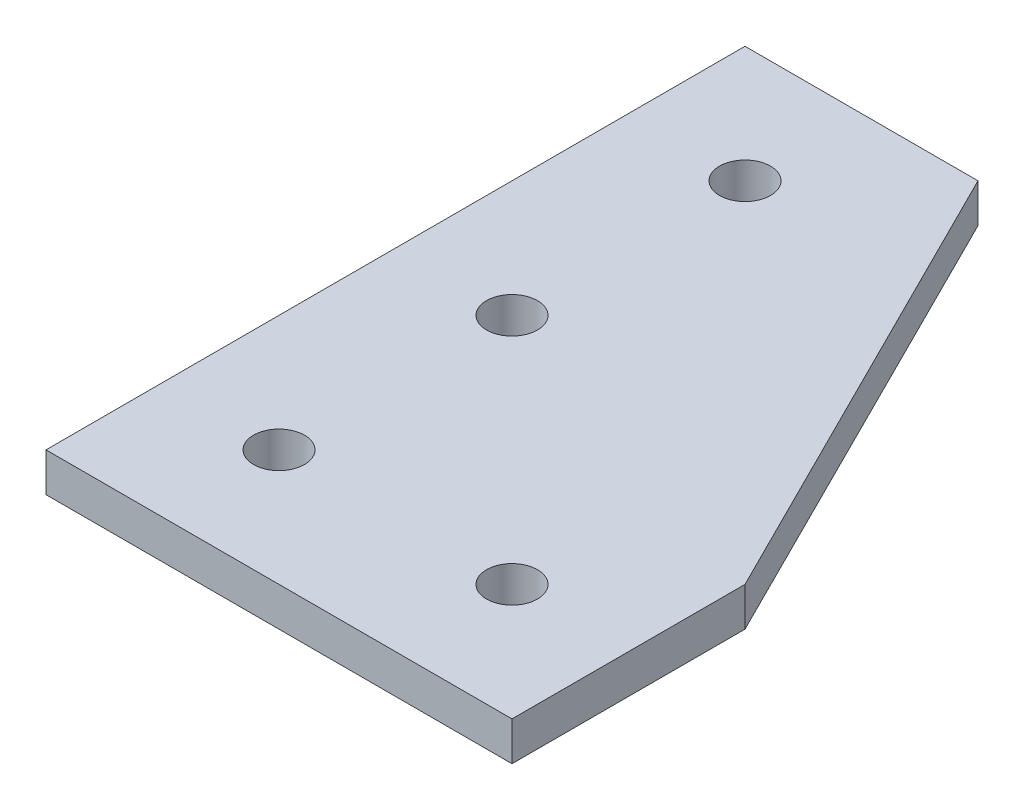
SolidWorks part; units mm, degrees
material "6105-T5 Aluminum"
ref_plane "Front Plane" through (0, 0, 0) normal (0, 0, 1) x (1, 0, 0)
ref_plane "Top Plane" through (0, 0, 0) normal (0, 1, 0) x (1, 0, 0)
ref_plane "Right Plane" through (0, 0, 0) normal (1, 0, 0) x (0, 0, -1)
sketch "Sketch1" plane through (0, 0, 0) normal (0, 0, 1) x (1, 0, 0)
  line L1 (-38.1, -3.175) -> (38.1, -3.175)
  line L2 (-38.1, -3.175) -> (-38.1, 3.175)
  line L3 (-38.1, 3.175) -> (38.1, 3.175)
  line L4 (38.1, -3.175) -> (38.1, 3.175)
  line L5 (-38.1, -3.175) -> (38.1, 3.175) construction
  line L6 (-38.1, 3.175) -> (38.1, -3.175) construction
  point P0 (0, 0)
  dimension "D1" = 76.2
  dimension "D2" = 6.35
extrude "Boss-Extrude1" add sketch "Sketch1" along normal mid plane 114.3
sketch "Sketch8" plane through (0, 3.175, 0) normal (0, 1, 0) x (-1, 0, 0)
  line L0 (0, -57.15) -> (-38.1, 19.05)
  line L1 (-38.1, -57.15) -> (38.1, -57.15) construction
  line L2 (-38.1, 57.15) -> (-38.1, -57.15) construction
  line L3 (-38.1, 19.05) -> (-38.1, -57.15)
  line L4 (-38.1, -57.15) -> (0, -57.15)
  line L5 (-38.1, 57.15) -> (38.1, 57.15) construction
  line L6 (38.1, 57.15) -> (38.1, -57.15) construction
  dimension "D1" = 38.1
  dimension "D2" = 38.1
extrude "Cut-Extrude3" cut sketch "Sketch8" against normal blind 7.62
hole_wizard "21/64 (0.32813) Diameter Hole1" positions "Sketch10" profile "Sketch9" hole size "21/64" standard "Ansi Inch"
sketch "Sketch10" plane through (0, 3.175, 0) normal (0, 1, 0) x (-1, 0, 0)
  point P0 (19.05, 38.1)
  dimension "D1" = 38.1
  dimension "D2" = 19.05
sketch "Sketch9" plane through (-19.05, 3.175, 38.1) normal (1, 0, 0) x (0, 0, 1)
  line L0 (0, 0) -> (0, 8.8539)
  line L1 (0, 8.8539) -> (4.1673, 6.35)
  line L2 (4.1673, 6.35) -> (4.1673, 0)
  line L5 (4.1673, 0) -> (0, 0)
  line L10 (0, 8.8539) -> (-4.1673, 6.35) construction
  line L11 (0, -6.35) -> (0, 1.4053) construction
  dimension "Hole Dia." = 8.3345
  dimension "Hole Depth" = 6.35
  dimension "Drill Angle" = 118
pattern_linear "LPattern1" count 3 spacing 38.1 along (0, 0, -1) count 2 spacing 38.1 along (1, 0, 0) skipping (1, 1), (2, 1) of "21/64 (0.32813) Diameter Hole1"
